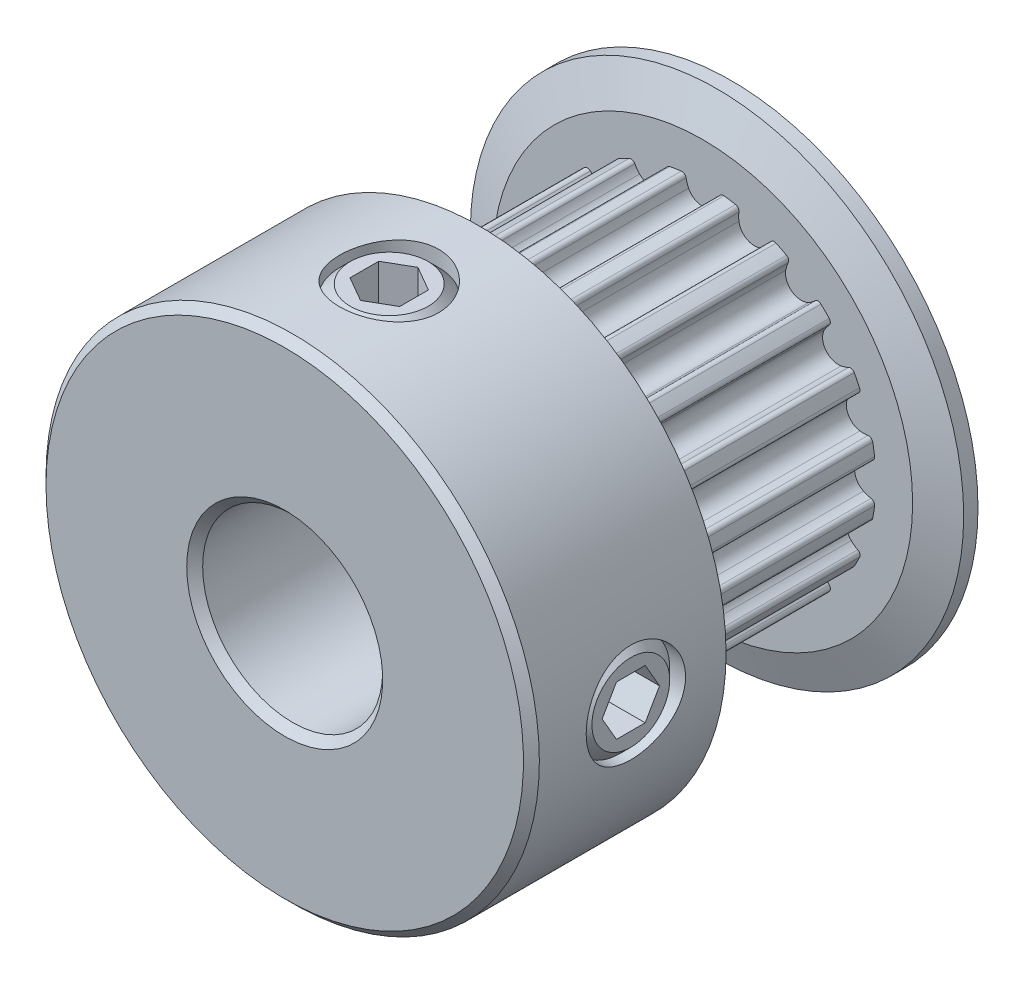
SolidWorks part; units mm, degrees
ref_plane "Front Plane" through (0, 0, 0) normal (0, 0, 1) x (1, 0, 0)
ref_plane "Top Plane" through (0, 0, 0) normal (0, 1, 0) x (1, 0, 0)
ref_plane "Right Plane" through (0, 0, 0) normal (1, 0, 0) x (0, 0, -1)
sketch "Sketch1" plane through (0, 0, 0) normal (0, 0, 1) x (1, 0, 0)
  line L1 (-1.7499, 5.3585) -> (1.7499, 5.3585) construction
  line L4 (0, 0) -> (0, 5.3585) construction
  line L5 (0, 5.3585) -> (0, 11.2144) construction
  line L6 (0, 6.3625) -> (1.9751, 6.0482) construction
  line L7 (1.9751, 6.0482) -> (2.6648, 5.8229) construction
  line L8 (1.9751, 6.0482) -> (1.7499, 5.3585) construction
  line L9 (-1.9751, 6.0482) -> (-1.7499, 5.3585) construction
  line L10 (-1.8963, 5.8067) -> (-2.841, 8.6995)
  line L11 (-2.841, 8.6995) -> (2.841, 8.6995)
  line L12 (2.841, 8.6995) -> (1.8963, 5.8067)
  circle A0 centre (0, 0) radius 6.3625 construction
  circle A1 centre (0, 0) radius 8.6995 construction
  circle A2 centre (0, 0) radius 6.1085 construction
  arc A3 (-0.4989, 5.6703) -> (0.4989, 5.6703) centre (0, 5.9135) ccw
  arc A4 (-0.4989, 5.6703) -> (-0.5855, 5.9387) centre (0.4, 6.1085) cw
  arc A5 (-1.8963, 5.8067) -> (-0.7518, 6.0621) centre (0, 0) cw
  arc A6 (-0.5855, 5.9387) -> (-0.7518, 6.0621) centre (-0.7333, 5.9132) ccw
  arc A7 (1.8963, 5.8067) -> (0.7518, 6.0621) centre (0, 0) ccw
  arc A8 (0.5855, 5.9387) -> (0.7518, 6.0621) centre (0.7333, 5.9132) cw
  arc A9 (0.4989, 5.6703) -> (0.5855, 5.9387) centre (-0.4, 6.1085) ccw
  point P6 (0, 20.9083)
  point P11 (0, 6.3625)
  point P13 (0, 8.6995)
  point P14 (0, 6.1085)
  dimension "D1" = 9.6939
  dimension "D2" = 4.8519
sketch "Sketch2" plane through (0, 0, 0) normal (1, 0, 0) x (0, 0, -1)
  line L0 (-7.875, 3.175) -> (7.875, 3.175)
  line L1 (-7.875, 3.175) -> (-7.875, 8.6995)
  line L2 (-1.01, 8.6995) -> (-7.875, 8.6995)
  line L3 (-1.515, 3.175) -> (-1.515, 8.6995) construction
  line L4 (-1.515, 8.6995) -> (-0.505, 8.6995) construction
  line L5 (-0.505, 8.6995) -> (-0.505, 6.1085) construction
  line L6 (-0.505, 6.1085) -> (6.865, 6.1085)
  line L7 (6.865, 6.1085) -> (6.865, 8.6995) construction
  line L8 (6.865, 8.6995) -> (7.875, 8.6995) construction
  line L9 (7.875, 8.6995) -> (7.875, 3.175)
  line L10 (-7.875, 0) -> (7.875, 0) construction
  line L11 (7.37, 8.6995) -> (6.865, 7.404)
  line L12 (-0.505, 7.404) -> (-1.01, 8.6995)
  line L14 (-0.505, 7.404) -> (-0.505, 6.1085)
  line L15 (6.865, 6.1085) -> (6.865, 7.404)
  line L16 (7.37, 8.6995) -> (7.875, 8.6995)
  arc A0 (-0.505, 7.404) -> (-1.01, 8.6995) centre (-2.4192, 7.404) ccw construction
  arc A1 (6.865, 7.404) -> (7.37, 8.6995) centre (8.7792, 7.404) cw construction
  point P12 (-0.505, 7.404)
  point P14 (-1.01, 8.6995)
  point P20 (6.865, 7.404)
  point P21 (7.37, 8.6995)
  point P25 (6.865, 0)
  point P26 (-0.505, 0)
  dimension "OA" = 15.75
  dimension "Bore" = 6.35
  dimension "Outside Width" = 8.38
  dimension "Inside Width" = 7.37
revolve "Revolve1" add sketch "Sketch2" angle 360 mid plane about L10
sketch "Sketch3" plane through (0, 0, 0) normal (0, 0, 1) x (1, 0, 0)
  line L6 (2.841, 8.6995) -> (-2.841, 8.6995)
  line L7 (1.8963, 5.8067) -> (2.841, 8.6995)
  line L8 (-2.841, 8.6995) -> (-1.8963, 5.8067)
  line L9 (2.841, 8.6995) -> (-2.841, 8.6995)
  line L10 (1.8963, 5.8067) -> (2.841, 8.6995)
  line L11 (-2.841, 8.6995) -> (-1.8963, 5.8067)
  arc A8 (1.8963, 5.8067) -> (0.7518, 6.0621) centre (0, 0) ccw
  arc A9 (0.7518, 6.0621) -> (0.5855, 5.9387) centre (0.7333, 5.9132) ccw
  arc A10 (0.4989, 5.6703) -> (0.5855, 5.9387) centre (-0.4, 6.1085) ccw
  arc A11 (-0.4989, 5.6703) -> (0.4989, 5.6703) centre (0, 5.9135) ccw
  arc A12 (-0.5855, 5.9387) -> (-0.4989, 5.6703) centre (0.4, 6.1085) ccw
  arc A13 (-0.5855, 5.9387) -> (-0.7518, 6.0621) centre (-0.7333, 5.9132) ccw
  arc A14 (-0.7518, 6.0621) -> (-1.8963, 5.8067) centre (0, 0) ccw
  arc A15 (1.8963, 5.8067) -> (0.7518, 6.0621) centre (0, 0) ccw
  arc A16 (0.7518, 6.0621) -> (0.5855, 5.9387) centre (0.7333, 5.9132) ccw
  arc A17 (0.4989, 5.6703) -> (0.5855, 5.9387) centre (-0.4, 6.1085) ccw
  arc A18 (-0.4989, 5.6703) -> (0.4989, 5.6703) centre (0, 5.9135) ccw
  arc A19 (-0.5855, 5.9387) -> (-0.4989, 5.6703) centre (0.4, 6.1085) ccw
  arc A20 (-0.5855, 5.9387) -> (-0.7518, 6.0621) centre (-0.7333, 5.9132) ccw
  arc A21 (-0.7518, 6.0621) -> (-1.8963, 5.8067) centre (0, 0) ccw
  dimension "D1" = 0
extrude "Cut-Extrude1" cut sketch "Sketch3" against normal up to vertex (6.865 mm away) from vertex up to point (0, 6.1085, -6.865) starting at point (0, 6.1085, 0.505)
pattern_circular "CirPattern1" count 20 over 360 about axis through (0, 0, 7.875) along (0, 0, 1) of "Cut-Extrude1"
sketch "Sketch4" plane through (0, 0, 0) normal (1, 0, 0) x (0, -1, 0)
  line L0 (0, -0.505) -> (0, -7.875) construction
  line L1 (-3.175, -7.875) -> (3.175, -7.875) construction
  line L2 (7.404, -0.505) -> (-7.404, -0.505) construction
  circle A0 centre (0, -4.19) radius 1.7526
extrude "Cut-Extrude2" cut sketch "Sketch4" along normal through all
ref_plane "Plane1" through (0, 0, 4.19) normal (0, 0, 1) x (1, 0, 0)
sketch "Sketch5" plane through (0, 0, 4.19) normal (0, 0, 1) x (1, 0, 0)
  line L0 (0, 0) -> (0, 8.6995) construction
  line L1 (3.175, -1.3716) -> (3.175, 0)
  line L2 (3.556, -1.7526) -> (8.1401, -1.7526)
  line L3 (3.175, 0) -> (8.6995, 0) construction
  line L4 (3.175, 0) -> (8.5211, 0)
  line L5 (8.5211, 0) -> (8.5211, -1.3716)
  line L6 (3.556, -1.7526) -> (3.175, -1.3716)
  line L7 (8.5211, -1.3716) -> (8.1401, -1.7526)
  circle A0 centre (0, 0) radius 8.6995 construction
  circle A1 centre (0, 0) radius 3.175 construction
  point P2 (3.175, -1.7526)
  point P11 (8.5211, -1.7526)
revolve "Revolve2" add sketch "Sketch5" angle 360 mid plane about L4
sketch "Sketch6" plane through (8.5211, 5.3841, 0) normal (-1, 0, 0) x (0, -1, 0)
  line L1 (5.3841, 5.2019) -> (4.5078, 4.6959)
  line L2 (4.5078, 4.6959) -> (4.5078, 3.6841)
  line L3 (4.5078, 3.6841) -> (5.3841, 3.1781)
  line L4 (5.3841, 3.1781) -> (6.2604, 3.6841)
  line L5 (6.2604, 3.6841) -> (6.2604, 4.6959)
  line L6 (6.2604, 4.6959) -> (5.3841, 5.2019)
  circle A0 centre (5.3841, 4.19) radius 0.8763 construction
  dimension "D1" = 1.7526
extrude "Cut-Extrude3" cut sketch "Sketch6" along normal blind 1.3144
pattern_circular "CirPattern3" count 2 over 90 about axis through (0, 0, 7.875) along (0, 0, 1) of "Cut-Extrude2", "Revolve2", "Cut-Extrude3"
chamfer "Chamfer1" distance 0.2807 angle 45 2 edges at (3.175, 0, 7.875) (8.6995, 0, 7.875)
ref_axis "Center Axis 1" through (0, 0, -7.875) along (0, 0, 1)
ref_plane "Contact Plane 1" through (0, 0, 7.875) normal (0, 0, 1) x (1, 0, 0)
ref_plane "Contact Plane 2" through (0, 0, -7.875) normal (0, 0, -1) x (-1, 0, 0)
equation "\"D2@Sketch1\"= \"D1@Sketch1\" / 2"
equation "\"D1@Sketch6\" = \"Set Screw@Sketch4\" / 2"
equation "\"D1@Cut-Extrude3\" = \"D1@Sketch6\"*.75"
